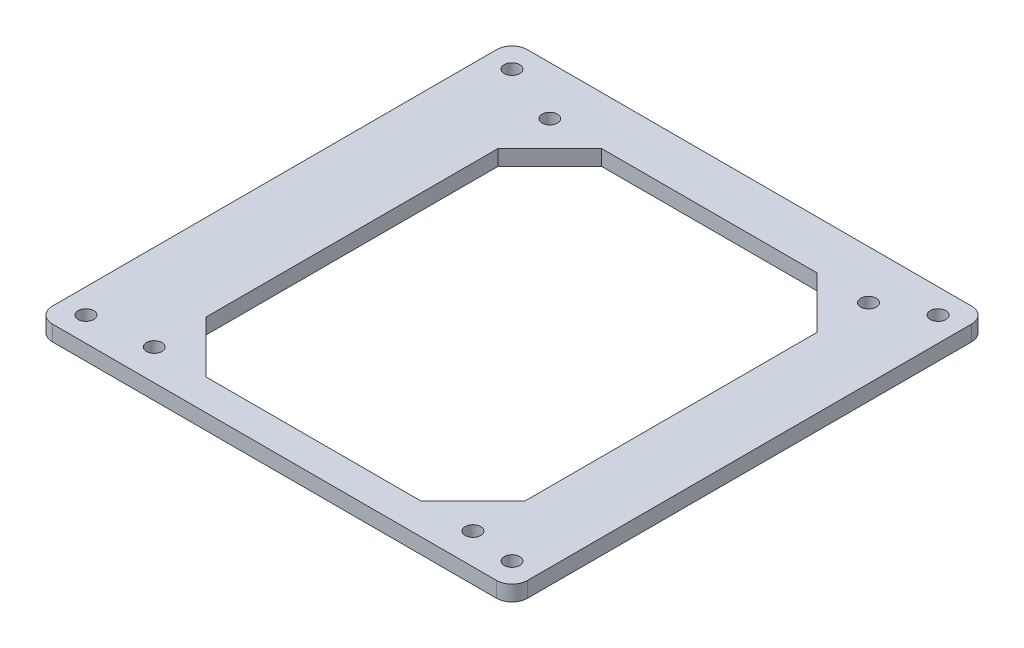
SolidWorks part; units mm, degrees
ref_plane "前基準面" through (0, 0, 0) normal (0, 0, 1) x (1, 0, 0)
ref_plane "上基準面" through (0, 0, 0) normal (0, 1, 0) x (1, 0, 0)
ref_plane "右基準面" through (0, 0, 0) normal (1, 0, 0) x (0, 0, -1)
sketch "草圖1" plane through (0, 0, 0) normal (0, 1, 0) x (1, 0, 0)
  line L0 (-41.25, 41.25) -> (41.25, 41.25) construction
  line L1 (-46, 46) -> (46, 46)
  line L2 (-46, 46) -> (-46, -46)
  line L3 (-46, -46) -> (46, -46)
  line L4 (46, 46) -> (46, -46)
  line L5 (-46, 46) -> (46, -46) construction
  line L6 (-46, -46) -> (46, 46) construction
  line L7 (-41.25, 41.25) -> (-41.25, -41.25) construction
  line L8 (-41.25, 41.25) -> (-41.25, 46) construction
  line L9 (-41.25, 41.25) -> (-46, 41.25) construction
  circle A0 centre (-41.25, 41.25) radius 1.5
  circle A1 centre (41.25, 41.25) radius 1.5
  circle A2 centre (41.25, -41.25) radius 1.5
  circle A3 centre (-41.25, -41.25) radius 1.5
  point P0 (0, 0)
  dimension "D7" = 3
  dimension "D1" = 92
  dimension "D2" = 92
  dimension "D5" = 82.5
  dimension "D6" = 82.5
  dimension "D8" = 4.75
  dimension "D3" = 2
  dimension "D4" = 2
extrude "填料-伸長1" add sketch "草圖1" along normal blind 3
sketch "草圖2" plane through (0, 3, 0) normal (0, 1, 0) x (1, 0, 0)
  line L0 (0, 0) -> (55.2066, 0) construction
  line L1 (55.2066, 0) -> (-60.768, 0) construction
  line L2 (0, 0) -> (0, 56.6444) construction
  line L3 (0, 56.6444) -> (0, -55.3423) construction
  line L5 (-36.5, 36.5) -> (36.5, 36.5)
  line L6 (-36.5, 36.5) -> (-36.5, -36.5)
  line L7 (-36.5, -36.5) -> (36.5, -36.5)
  line L8 (36.5, 36.5) -> (36.5, -36.5)
  line L9 (-36.5, 36.5) -> (36.5, -36.5) construction
  line L10 (-36.5, -36.5) -> (36.5, 36.5) construction
  dimension "D1" = 73
  dimension "D2" = 73
sketch "草圖3" plane through (0, 3, 0) normal (0, 1, 0) x (1, 0, 0)
  line L0 (36.5, 36.5) -> (36.5, -36.5) construction
  line L1 (-33.35, 50.6) -> (36.5, 50.6)
  line L2 (-33.35, 50.6) -> (-33.35, -49.85)
  line L3 (-33.35, -49.85) -> (36.5, -49.85)
  line L4 (36.5, 50.6) -> (36.5, -49.85)
  line L5 (-33.35, 46) -> (36.5, 46)
  line L6 (46, 46) -> (-46, 46) construction
  line L7 (-29.285, 36.6) -> (32.435, 36.6) construction
  line L8 (-29.285, 36.6) -> (-29.285, -40) construction
  line L9 (-29.285, 36.6) -> (-33.35, 36.6) construction
  line L10 (32.435, 36.6) -> (36.5, 36.6) construction
  point P10 (-29.285, 36.6)
  point P14 (32.435, 36.6)
  point P15 (32.435, -40)
  point P16 (-29.285, -40)
  dimension "D1" = 69.85
  dimension "D2" = 100.45
  dimension "D3" = 4.6
  dimension "D7" = 61.72
  dimension "D8" = 76.6
  dimension "D9" = 9.4
  dimension "D5" = 2
  dimension "D6" = 2
sketch "草圖4" plane through (0, 3, 0) normal (0, 1, 0) x (1, 0, 0)
  line L0 (-29.285, 26.6) -> (-19.285, 36.6)
  line L1 (-19.285, 36.6) -> (22.435, 36.6)
  line L2 (-29.285, 26.6) -> (-29.285, -30)
  line L3 (-19.285, -40) -> (22.435, -40)
  line L4 (32.435, 26.6) -> (32.435, -30)
  line L5 (22.435, 36.6) -> (32.435, 26.6)
  line L6 (22.435, -40) -> (32.435, -30)
  line L7 (-29.285, -30) -> (-19.285, -40)
  point P0 (-29.285, 36.6)
  point P1 (32.435, -40)
  point P2 (-29.285, -40)
  point P3 (32.435, 36.6)
hole_wizard "Ø3.0mm 定位孔1" positions "3D草圖1" profile "草圖5" hole size "Ø3.0" standard "GB" end condition through all
sketch3d "3D草圖1"
  point P0 (-29.285, 3, -36.6)
  point P3 (32.435, 3, -36.6)
  point P6 (32.435, 3, 40)
  point P9 (-29.285, 3, 40)
sketch "草圖5" plane through (-29.285, 3, -36.6) normal (1, 0, 0) x (0, 0, 1)
  line L0 (0, 0) -> (0, 3)
  line L1 (0, 3) -> (1.5, 3)
  line L2 (1.5, 3) -> (1.5, 0)
  line L5 (1.5, 0) -> (0, 0)
  line L11 (0, -6.35) -> (0, 107.95) construction
  dimension "貫穿孔直徑" = 3
  dimension "貫穿孔深度" = 3
extrude "除料-伸長1" cut sketch "草圖4" against normal through all
fillet "圓角1" radius 3 4 edges at (-46, 1.5, 46) (46, 1.5, 46) (46, 1.5, -46) (-46, 1.5, -46)
